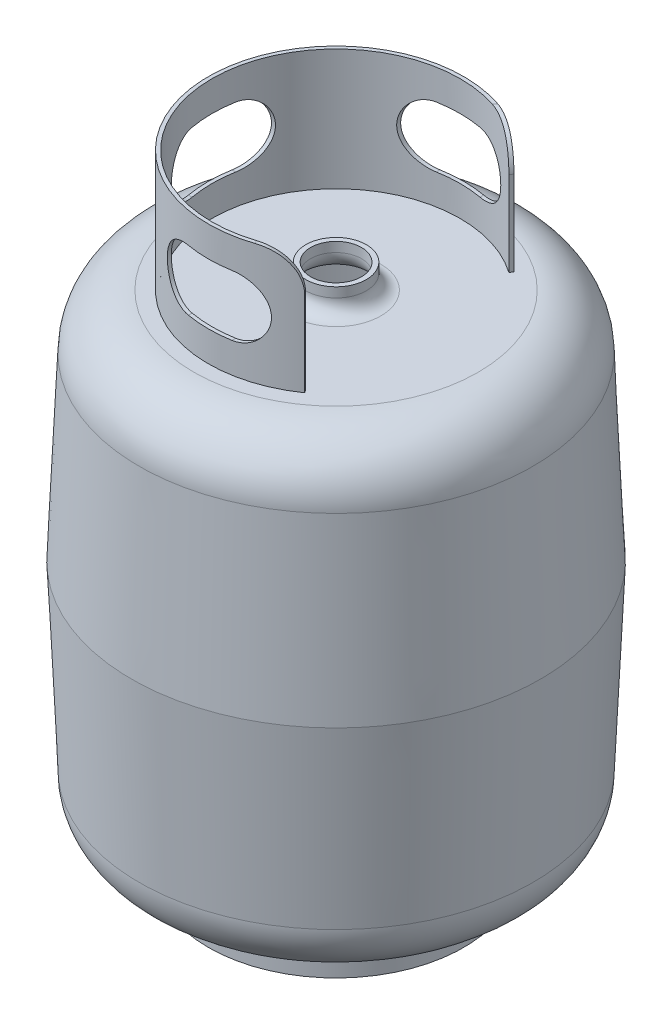
SolidWorks part; units mm, degrees
ref_plane "Front Plane" through (0, 0, 0) normal (0, 0, 1) x (1, 0, 0)
ref_plane "Top Plane" through (0, 0, 0) normal (0, 1, 0) x (1, 0, 0)
ref_plane "Right Plane" through (0, 0, 0) normal (1, 0, 0) x (0, 0, -1)
sketch "Sketch1" plane through (0, 0, 0) normal (0, 0, 1) x (1, 0, 0)
  line L0 (0, 0) -> (-82.6302, 0) construction
  line L1 (0, 0) -> (0, 70.7172) construction
  line L2 (-162.5, 148.8393) -> (-168.9985, 0)
  line L3 (-21, 213.75) -> (-21, 205.75)
  line L4 (-117.5001, 193.75) -> (-37, 193.75)
  line L5 (-25, 205.75) -> (-25, 213.75)
  line L6 (-25, 213.75) -> (-21, 213.75)
  line L7 (-37, 189.75) -> (-117.5001, 189.75)
  line L8 (-158.5001, 148.75) -> (-164.9947, 0)
  line L9 (-117.5001, -189.75) -> (0, -189.75)
  line L10 (0, -189.75) -> (0, -193.75)
  line L11 (-158.5001, -148.75) -> (-164.9947, 0)
  line L12 (-162.5, -148.8393) -> (-168.9985, 0)
  line L13 (0, -193.75) -> (-117.5001, -193.75)
  arc A0 (-162.5, 148.8393) -> (-117.5001, 193.75) centre (-117.5001, 148.75) cw
  arc A1 (-37, 193.75) -> (-25, 205.75) centre (-37, 205.75) ccw
  arc A2 (-37, 189.75) -> (-21, 205.75) centre (-37, 205.75) ccw
  arc A3 (-117.5001, 189.75) -> (-158.5001, 148.75) centre (-117.5001, 148.75) ccw
  arc A4 (-117.5001, -189.75) -> (-158.5001, -148.75) centre (-117.5001, -148.75) cw
  arc A5 (-162.5, -148.8393) -> (-117.5001, -193.75) centre (-117.5001, -148.75) ccw
  point P14 (-162.5, 193.75)
  point P16 (-25, 193.75)
  dimension "D5" = 45
  dimension "D6" = 12
  dimension "D1" = 20
  dimension "D2" = 387.5
  dimension "D3" = 92.5
  dimension "D4" = 325
  dimension "D7" = 50
  dimension "D8" = 4
  dimension "D9" = 4
  dimension "D10" = 4
revolve "Revolve1" add sketch "Sketch1" angle 360 about L1
sketch "Sketch2" plane through (0, 193.75, 0) normal (0, 1, 0) x (1, 0, 0)
  line L0 (0, 0) -> (117.5001, 0) construction
  line L1 (58.7916, 83.9632) -> (60.5124, 86.4206)
  line L2 (58.7916, -83.9632) -> (60.5124, -86.4206)
  arc A0 (60.5124, 86.4206) -> (60.5124, -86.4206) centre (0, 0) ccw
  circle A1 centre (0, 0) radius 117.5001 construction
  arc A2 (58.7916, 83.9632) -> (58.7916, -83.9632) centre (0, 0) ccw
  dimension "D1" = 12
  dimension "D2" = 3
  dimension "D3" = 55
  dimension "D4" = 55
extrude "Boss-Extrude1" add sketch "Sketch2" along normal blind 100
fillet "Fillet1" radius 30 1 edges at (59.652, 293.75, 85.1919)
fillet "Fillet2" radius 30 1 edges at (59.652, 293.75, -85.1919)
sketch "Sketch3" plane through (0, 0, 0) normal (0, 0, 1) x (1, 0, 0)
  line L0 (17.9999, 243.75) -> (-18.0001, 243.75) construction
  line L1 (17.9999, 218.75) -> (-18.0001, 218.75)
  line L2 (17.9999, 268.75) -> (-18.0001, 268.75)
  line L4 (-105.5001, 293.75) -> (-105.5001, 193.75) construction
  arc A0 (17.9999, 218.75) -> (17.9999, 268.75) centre (17.9999, 243.75) ccw
  arc A1 (-18.0001, 268.75) -> (-18.0001, 218.75) centre (-18.0001, 243.75) ccw
  point P2 (-0.0001, 243.75)
  point P7 (-43.0001, 243.75)
  point P8 (42.9999, 243.75)
  dimension "D1" = 86
  dimension "D2" = 50
  dimension "D3" = 50
  dimension "D4" = 18
  dimension "D6" = 105.5
extrude "Cut-Extrude1" cut sketch "Sketch3" against normal through all both and the other way through all
sketch "Sketch4" plane through (0, 0, 0) normal (1, 0, 0) x (0, 0, -1)
  line L0 (-17.9999, 243.75) -> (18.0001, 243.75) construction
  line L1 (-17.9999, 268.75) -> (18.0001, 268.75)
  line L2 (-17.9999, 218.75) -> (18.0001, 218.75)
  line L3 (105.5001, 193.75) -> (-105.5001, 193.75) construction
  line L4 (105.5001, 193.75) -> (105.5001, 218.75) construction
  arc A0 (-17.9999, 268.75) -> (-17.9999, 218.75) centre (-17.9999, 243.75) ccw
  arc A1 (18.0001, 218.75) -> (18.0001, 268.75) centre (18.0001, 243.75) ccw
  point P2 (0.0001, 243.75)
  point P9 (43.0001, 243.75)
  point P10 (-42.9999, 243.75)
  dimension "D1" = 25
  dimension "D2" = 50
  dimension "D3" = 86
  dimension "D4" = 105.5
extrude "Cut-Extrude2" cut sketch "Sketch4" against normal through all both
sketch "Sketch5" plane through (0, -193.75, 0) normal (0, -1, 0) x (1, 0, 0)
  circle A0 centre (0, 0) radius 105.5001
  circle A1 centre (0, 0) radius 117.5001 construction
  circle A2 centre (0, 0) radius 102.5001
  dimension "D1" = 12
  dimension "D2" = 3
extrude "Boss-Extrude2" add sketch "Sketch5" along normal blind 30
